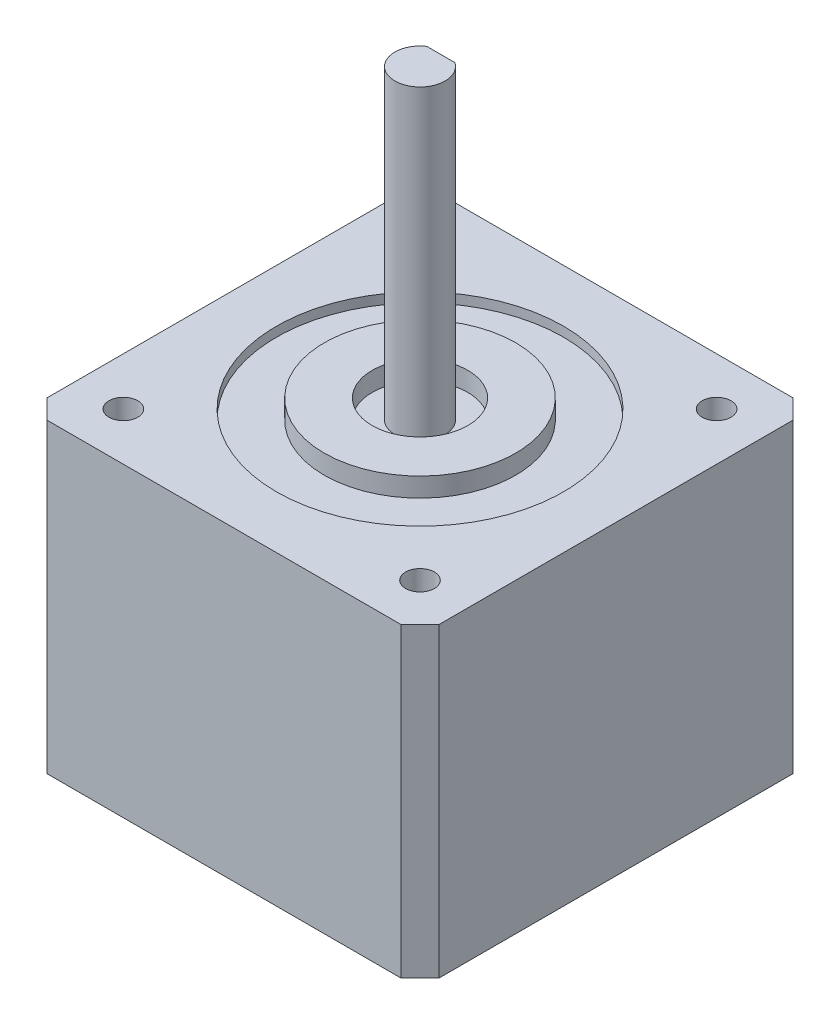
SolidWorks part; units mm, degrees
ref_plane "Front Plane" through (0, 0, 0) normal (0, 0, 1) x (1, 0, 0)
ref_plane "Top Plane" through (0, 0, 0) normal (0, 1, 0) x (1, 0, 0)
ref_plane "Right Plane" through (0, 0, 0) normal (1, 0, 0) x (0, 0, -1)
sketch "Sketch1" plane through (0, 0, 0) normal (0, 1, 0) x (1, 0, 0)
  line L0 (-20.5, 18.5) -> (-18.5, 20.5)
  line L1 (-18.5, -20.5) -> (18.5, -20.5)
  line L2 (-20.5, -18.5) -> (-20.5, 18.5)
  line L3 (-18.5, 20.5) -> (18.5, 20.5)
  line L4 (20.5, -18.5) -> (20.5, 18.5)
  line L5 (-20.5, -20.5) -> (20.5, 20.5) construction
  line L6 (-20.5, 20.5) -> (20.5, -20.5) construction
  line L7 (-18.5, -20.5) -> (-20.5, -18.5)
  line L8 (18.5, -20.5) -> (20.5, -18.5)
  line L9 (20.5, 18.5) -> (18.5, 20.5)
  point P0 (0, 0)
  dimension "D1" = 41
  dimension "D2" = 41
extrude "Boss-Extrude1" add sketch "Sketch1" along normal blind 32
sketch "Sketch2" plane through (0, 32, 0) normal (0, 1, 0) x (-1, 0, 0)
  circle A0 centre (0, 0) radius 15
extrude "Cut-Extrude1" cut sketch "Sketch2" against normal blind 1
sketch "Sketch3" plane through (0, 31, 0) normal (0, 1, 0) x (1, 0, 0)
  circle A0 centre (0, 0) radius 10
  circle A1 centre (0, 0) radius 5
extrude "Boss-Extrude2" add sketch "Sketch3" along normal blind 2
sketch "Sketch4" plane through (0, 31, 0) normal (0, 1, 0) x (1, 0, 0)
  line L0 (-1.471, 2.1754) -> (1.471, 2.1754)
  arc A0 (-1.471, 2.1754) -> (1.471, 2.1754) centre (0, 0) ccw
extrude "Boss-Extrude3" add sketch "Sketch4" along normal blind 32
hole_wizard "Ø3.0 (3) Diameter Hole1" positions "Sketch6" profile "Sketch5" hole size "Ø3.0" standard "Ansi Metric"
sketch "Sketch6" plane through (0, 32, 0) normal (0, 1, 0) x (-1, 0, 0)
  arc A0 (1.471, -2.1754) -> (-1.471, -2.1754) centre (0, 0) ccw construction
  point P0 (-15.5, -15.5)
  point P1 (15.5, -15.5)
  point P3 (15.5, 15.5)
  point P5 (-15.5, 15.5)
  dimension "D3" = 15.5
  dimension "D1" = 31
  dimension "D2" = 31
  dimension "D4" = 15.5
sketch "Sketch5" plane through (15.5, 32, -15.5) normal (1, 0, 0) x (0, 0, 1)
  line L0 (0, 0) -> (0, 5.9013)
  line L1 (0, 5.9013) -> (1.5, 5)
  line L2 (1.5, 5) -> (1.5, 0)
  line L5 (1.5, 0) -> (0, 0)
  line L10 (0, 5.9013) -> (-1.5, 5) construction
  line L11 (0, -6.35) -> (0, 107.95) construction
  dimension "Hole Dia." = 3
  dimension "Hole Depth" = 5
  dimension "Drill Angle" = 118
ref_axis "Motor Axis" through (0, 63, 0) along (0, -1, 0)
